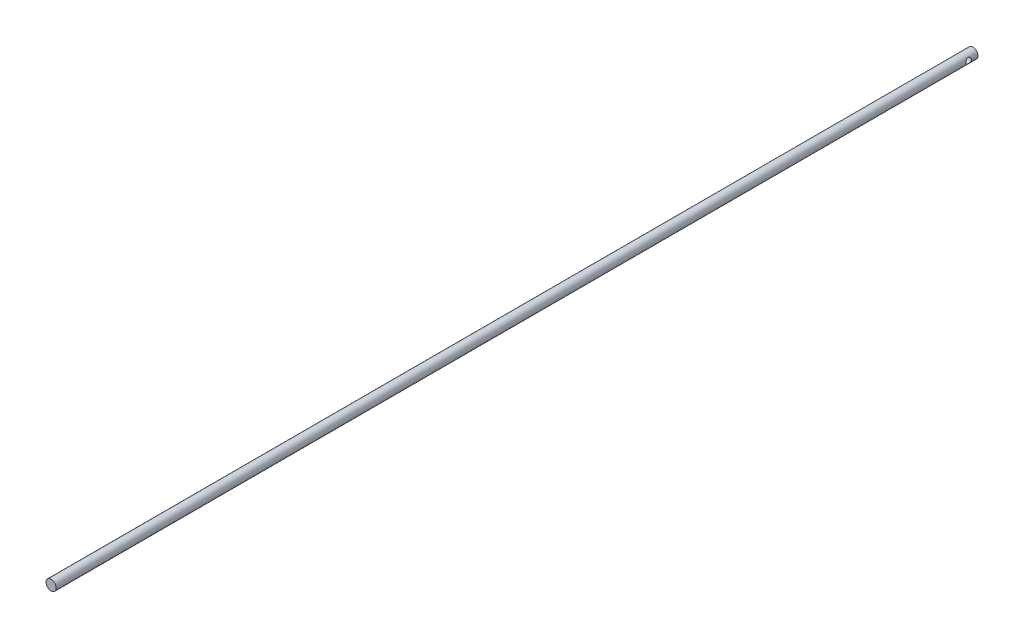
SolidWorks part; units mm, degrees
ref_plane "Front Plane" through (0, 0, 0) normal (0, 0, 1) x (1, 0, 0)
ref_plane "Top Plane" through (0, 0, 0) normal (0, 1, 0) x (1, 0, 0)
ref_plane "Right Plane" through (0, 0, 0) normal (1, 0, 0) x (0, 0, -1)
sketch "Sketch1" plane through (0, 0, 0) normal (0, 0, 1) x (1, 0, 0)
  circle A0 centre (0, 0) radius 1.397
  dimension "D1" = 2.794
extrude "Rod" add sketch "Sketch1" along normal blind 254
sketch "Sketch2" plane through (0, 0, 0) normal (0, 1, 0) x (1, 0, 0)
  line L0 (1.397, -254) -> (1.397, 0) construction
  line L1 (0.5715, 0) -> (1.397, 0)
  line L2 (0.5715, 0) -> (0.5715, -7.62)
  line L3 (0.5715, -7.62) -> (1.397, -7.62)
  line L4 (1.397, 0) -> (1.397, -7.62)
  line L6 (-0.9525, 0) -> (-1.778, 0)
  line L7 (-0.9525, 0) -> (-0.9525, -7.62)
  line L8 (-0.9525, -7.62) -> (-1.778, -7.62)
  line L9 (-1.778, 0) -> (-1.778, -7.62)
  dimension "D1" = 3.175
  dimension "D2" = 1.524
  dimension "D3" = 7.62
extrude "Flats" [suppressed] cut sketch "Sketch2" against normal through all and the other way through all
sketch "Sketch3" plane through (0, 0, 0) normal (1, 0, 0) x (0, 0, -1)
  circle A0 centre (-2.54, 0) radius 0.762
  dimension "D1" = 1.524
  dimension "D2" = 2.54
extrude "Hole" cut sketch "Sketch3" against normal up to next and the other way up to next
